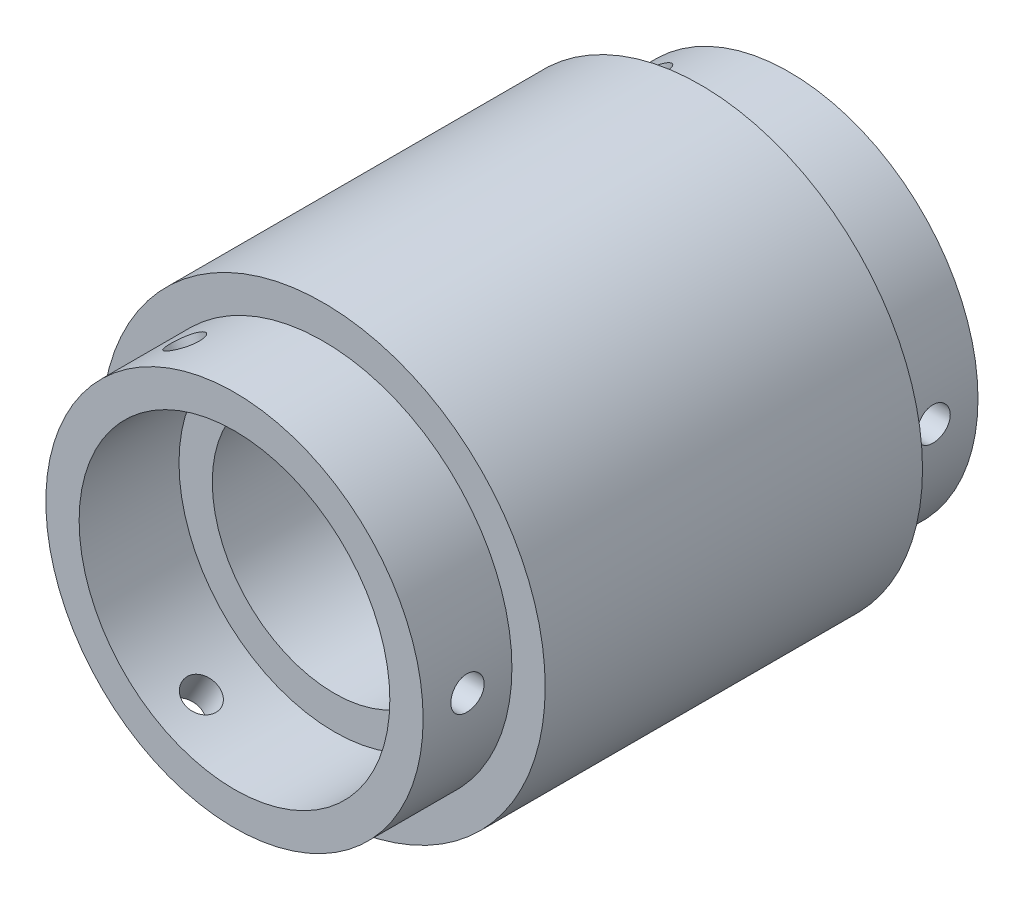
SolidWorks part; units mm, degrees
ref_plane "Płaszczyzna przednia" through (0, 0, 0) normal (0, 0, 1) x (1, 0, 0)
ref_plane "Płaszczyzna górna" through (0, 0, 0) normal (0, 1, 0) x (1, 0, 0)
ref_plane "Płaszczyzna prawa" through (0, 0, 0) normal (1, 0, 0) x (0, 0, -1)
sketch "Sketch1" plane through (0, 0, 0) normal (0, 0, 1) x (1, 0, 0)
  circle A0 centre (0, 0) radius 20
  dimension "D1" = 40
extrude "Boss-Extrude1" add sketch "Sketch1" along normal mid plane 50
hole_wizard "Hole1" positions "Sketch2" profile "Sketch3" legacy end condition through all
sketch "Sketch2" plane through (0, 0, 25) normal (0, 0, 1) x (1, 0, 0)
  point P0 (0, 0)
sketch "Sketch3" plane through (0, 0, 25) normal (1, 0, 0) x (0, -1, 0)
  line L0 (0, 0) -> (0, 56.6095)
  line L1 (0, 56.6095) -> (11, 50)
  line L2 (11, 50) -> (11, 9)
  line L3 (11, 9) -> (14, 9)
  line L4 (14, 0) -> (0, 0)
  line L5 (0, -11.3109) -> (0, 121.1557) construction
  line L6 (0, 56.6095) -> (-11, 50) construction
  line L7 (14, 9) -> (14, 0)
  dimension "Depth" = 50
  dimension "Drill Angle" = 118
  dimension "Diameter" = 22
  dimension "C-Bore Diameter" = 28
  dimension "C-Bore Depth" = 9
sketch "Sketch4" plane through (0, 0, 25) normal (0, 0, 1) x (1, 0, 0)
  circle A0 centre (0, 0) radius 20
  circle A1 centre (0, 0) radius 17
  circle A2 centre (0, 0) radius 20 construction
  dimension "D1" = 3
extrude "Cut-Extrude1" cut sketch "Sketch4" against normal blind 8
mirror "Mirror2" about plane through (0, 0, 0) normal (0, 0, 1) of "Cut-Extrude1", "Hole1"
sketch "Sketch5" plane through (0, 0, 0) normal (1, 0, 0) x (0, 0, -1)
  line L0 (-21, 0) -> (21, 0) construction
  line L3 (-25, 17) -> (-25, -17) construction
  circle A0 centre (-21, 0) radius 1.5
  circle A1 centre (21, 0) radius 1.5
  dimension "D2" = 3
  dimension "D3" = 3
  dimension "D1" = 4
extrude "Cut-Extrude2" cut sketch "Sketch5" along normal up to surface (17 mm away) up to face at (17, 0, -17)
pattern_circular "CirPattern1" count 3 over 360 about axis through (0, 0, 25) along (0, 0, 1) of "Cut-Extrude2"
